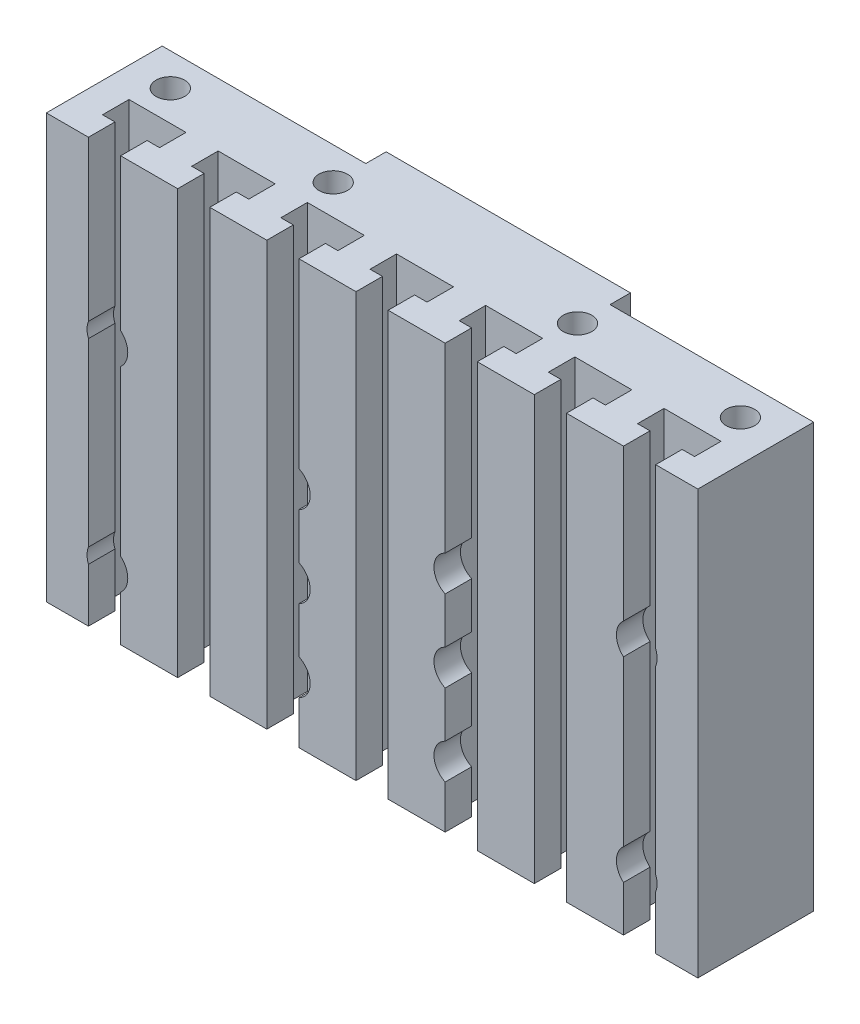
SolidWorks part; units mm, degrees
ref_plane "Front Plane" through (0, 0, 0) normal (0, 0, 1) x (1, 0, 0)
ref_plane "Top Plane" through (0, 0, 0) normal (0, 1, 0) x (1, 0, 0)
ref_plane "Right Plane" through (0, 0, 0) normal (1, 0, 0) x (0, 0, -1)
sketch "Sketch1" plane through (0, 0, 0) normal (0, 0, 1) x (1, 0, 0)
  line L0 (0, 52) -> (0, -52) construction
  line L1 (-80, 52) -> (80, 52)
  line L2 (-80, 52) -> (-80, -52)
  line L3 (-80, -52) -> (80, -52)
  line L4 (80, 52) -> (80, -52)
  line L5 (-80, 52) -> (80, -52) construction
  line L6 (-80, -52) -> (80, 52) construction
  line L7 (20, 52) -> (20, -55.7258) construction
  circle A0 centre (20, -37) radius 2.5
  circle A1 centre (-20, -37) radius 2.5
  circle A2 centre (20, -17) radius 2.5
  circle A3 centre (20, 3) radius 2.5
  circle A4 centre (-20, 3) radius 2.5
  circle A5 centre (-20, -17) radius 2.5
  point P0 (0, 0)
  dimension "D4" = 5
  dimension "D1" = 160
  dimension "D2" = 104
  dimension "D3" = 40
  dimension "D5" = 15
  dimension "D6" = 20
  dimension "D7" = 20
extrude "Boss-Extrude1" add sketch "Sketch1" along normal blind 28.45
sketch "Sketch2" plane through (0, 52, 0) normal (0, 1, 0) x (1, 0, 0)
  line L0 (80, -28.45) -> (-80, -28.45) construction
  line L1 (-3.95, -28.45) -> (3.95, -28.45)
  line L2 (-3.95, -28.45) -> (-3.95, -21.95)
  line L4 (3.95, -28.45) -> (3.95, -21.95)
  line L5 (3.95, -21.95) -> (7, -21.95)
  line L6 (-7, -15.45) -> (7, -15.45)
  line L7 (-7, -15.45) -> (-7, -21.95)
  line L8 (-7, -21.95) -> (-3.95, -21.95)
  line L9 (7, -15.45) -> (7, -21.95)
  line L10 (0, 0) -> (0, -28.45) construction
  line L11 (80, 0) -> (-80, 0) construction
  line L12 (25.85, -28.45) -> (25.85, -21.95)
  line L13 (17.95, -28.45) -> (25.85, -28.45)
  line L14 (25.85, -21.95) -> (28.9, -21.95)
  line L15 (28.9, -15.45) -> (28.9, -21.95)
  line L16 (14.9, -15.45) -> (28.9, -15.45)
  line L17 (14.9, -15.45) -> (14.9, -21.95)
  line L18 (14.9, -21.95) -> (17.95, -21.95)
  line L19 (17.95, -28.45) -> (17.95, -21.95)
  line L20 (47.75, -28.45) -> (47.75, -21.95)
  line L21 (39.85, -28.45) -> (47.75, -28.45)
  line L22 (47.75, -21.95) -> (50.8, -21.95)
  line L23 (50.8, -15.45) -> (50.8, -21.95)
  line L24 (36.8, -15.45) -> (50.8, -15.45)
  line L25 (36.8, -15.45) -> (36.8, -21.95)
  line L26 (36.8, -21.95) -> (39.85, -21.95)
  line L27 (39.85, -28.45) -> (39.85, -21.95)
  line L28 (69.65, -28.45) -> (69.65, -21.95)
  line L29 (61.75, -28.45) -> (69.65, -28.45)
  line L30 (69.65, -21.95) -> (72.7, -21.95)
  line L31 (72.7, -15.45) -> (72.7, -21.95)
  line L32 (58.7, -15.45) -> (72.7, -15.45)
  line L33 (58.7, -15.45) -> (58.7, -21.95)
  line L34 (58.7, -21.95) -> (61.75, -21.95)
  line L35 (61.75, -28.45) -> (61.75, -21.95)
  line L36 (-28.9, -15.45) -> (-28.9, -21.95)
  line L37 (-28.9, -21.95) -> (-25.85, -21.95)
  line L38 (-25.85, -28.45) -> (-25.85, -21.95)
  line L39 (-28.9, -15.45) -> (-14.9, -15.45)
  line L40 (-14.9, -15.45) -> (-14.9, -21.95)
  line L41 (-17.95, -28.45) -> (-17.95, -21.95)
  line L42 (-25.85, -28.45) -> (-17.95, -28.45)
  line L43 (-17.95, -21.95) -> (-14.9, -21.95)
  line L44 (-50.8, -15.45) -> (-50.8, -21.95)
  line L45 (-50.8, -21.95) -> (-47.75, -21.95)
  line L46 (-47.75, -28.45) -> (-47.75, -21.95)
  line L47 (-50.8, -15.45) -> (-36.8, -15.45)
  line L48 (-36.8, -15.45) -> (-36.8, -21.95)
  line L49 (-39.85, -28.45) -> (-39.85, -21.95)
  line L50 (-47.75, -28.45) -> (-39.85, -28.45)
  line L51 (-39.85, -21.95) -> (-36.8, -21.95)
  line L52 (-72.7, -15.45) -> (-72.7, -21.95)
  line L53 (-72.7, -21.95) -> (-69.65, -21.95)
  line L54 (-69.65, -28.45) -> (-69.65, -21.95)
  line L55 (-72.7, -15.45) -> (-58.7, -15.45)
  line L56 (-58.7, -15.45) -> (-58.7, -21.95)
  line L57 (-61.75, -28.45) -> (-61.75, -21.95)
  line L58 (-69.65, -28.45) -> (-61.75, -28.45)
  line L59 (-61.75, -21.95) -> (-58.7, -21.95)
  point P14 (0, -15.45)
  dimension "D1" = 14
  dimension "D2" = 7.9
  dimension "D3" = 6.5
  dimension "D4" = 6.5
  dimension "D6" = 7.9
  dimension "D8" = 7.9
  dimension "D5" = 4
  dimension "D7" = 4
extrude "Cut-Extrude1" cut sketch "Sketch2" against normal through all
sketch "Sketch5" plane through (0, 0, 0) normal (0, 0, -1) x (-1, 0, 0)
  line L0 (0, 52) -> (0, -52) construction
  line L1 (-80, 52) -> (80, 52) construction
  line L2 (80, -52) -> (-80, -52) construction
  line L4 (-30, -52) -> (30, -52)
  line L5 (-30, -52) -> (-30, 52)
  line L6 (-30, 52) -> (30, 52)
  line L7 (30, -52) -> (30, 52)
  point P10 (0, 52)
  dimension "D1" = 60
extrude "Boss-Extrude2" add sketch "Sketch5" along normal blind 5
sketch "Sketch3" plane through (0, 0, 28.45) normal (0, 0, 1) x (1, 0, 0)
  circle A0 centre (-20, 3) radius 4.8
  circle A1 centre (20, 3) radius 4.8
  circle A2 centre (-20, -17) radius 4.8
  circle A3 centre (20, -17) radius 4.8
  circle A4 centre (-20, -37) radius 4.8
  circle A5 centre (20, -37) radius 4.8
  dimension "D1" = 9.6
extrude "Cut-Extrude2" cut sketch "Sketch3" against normal blind 7
sketch "Sketch4" plane through (0, 0, 15.45) normal (0, 0, 1) x (1, 0, 0)
  circle A0 centre (-20, 3) radius 4.8
  circle A1 centre (20, 3) radius 4.8
  circle A2 centre (-20, -17) radius 4.8
  circle A3 centre (20, -17) radius 4.8
  circle A4 centre (-20, -37) radius 4.8
  circle A5 centre (20, -37) radius 4.8
  dimension "D1" = 9.6
extrude "Cut-Extrude3" cut sketch "Sketch4" against normal blind 13.35 from surface starting at face at (-16.515, -10.2, 21.95)
sketch "Sketch6" plane through (0, 0, 0) normal (0, 0, 1) x (1, 0, 0)
  circle A0 centre (-20, 3) radius 2.5
  circle A1 centre (20, 3) radius 2.5
  circle A2 centre (-20, -17) radius 2.5
  circle A3 centre (20, -17) radius 2.5
  circle A4 centre (20, -37) radius 2.5
  circle A5 centre (-20, -37) radius 2.5
  dimension "D1" = 5
extrude "Cut-Extrude4" cut sketch "Sketch6" against normal through all
sketch "Sketch7" plane through (0, 52, 0) normal (0, 1, 0) x (1, 0, 0)
  line L0 (-80, -8) -> (80, -8) construction
  line L1 (-80, -28.45) -> (-80, 0) construction
  line L2 (80, -28.45) -> (80, 0) construction
  line L4 (-30, 0) -> (-80, 0) construction
  line L6 (0, 5) -> (0, -15.45) construction
  line L7 (-30, 5) -> (30, 5) construction
  line L8 (7, -15.45) -> (-7, -15.45) construction
  circle A0 centre (-70, -8) radius 3.5
  circle A1 centre (-30, -8) radius 3.5
  circle A2 centre (70, -8) radius 3.5
  circle A3 centre (30, -8) radius 3.5
  dimension "D1" = 7
  dimension "D3" = 40
  dimension "D2" = 10
  dimension "D4" = 8
extrude "Cut-Extrude5" cut sketch "Sketch7" against normal blind 12
sketch "Sketch8" plane through (0, -52, 0) normal (0, -1, 0) x (1, 0, 0)
  line L0 (80, 8) -> (-80, 8) construction
  line L1 (80, 28.45) -> (80, 0) construction
  line L2 (-80, 28.45) -> (-80, 0) construction
  line L3 (30, 0) -> (80, 0) construction
  line L6 (0, -5) -> (0, 15.45) construction
  line L7 (30, -5) -> (-30, -5) construction
  line L8 (7, 15.45) -> (-7, 15.45) construction
  circle A0 centre (70, 8) radius 3.5
  circle A1 centre (30, 8) radius 3.5
  circle A2 centre (-30, 8) radius 3.5
  circle A3 centre (-70, 8) radius 3.5
  dimension "D1" = 7
  dimension "D2" = 10
  dimension "D3" = 40
  dimension "D4" = 8
extrude "Cut-Extrude6" cut sketch "Sketch8" against normal blind 12
sketch "Sketch9" plane through (0, 0, 28.45) normal (0, 0, 1) x (1, 0, 0)
  line L0 (0, 47.1529) -> (0, -45.7832) construction
  line L1 (-80, -52) -> (-69.65, -52) construction
  line L2 (-65, 11) -> (65, 11) construction
  line L3 (-65, 11) -> (-65, -37) construction
  line L4 (-65, -37) -> (65, -37) construction
  line L5 (65, 11) -> (65, -37) construction
  circle A0 centre (-65, 11) radius 5
  circle A1 centre (-65, -37) radius 5
  circle A2 centre (65, -37) radius 5
  circle A3 centre (65, 11) radius 5
  point P3 (0, 11)
  point P8 (-65, -13)
  dimension "D3" = 10
  dimension "D1" = 130
  dimension "D2" = 48
  dimension "D4" = 15
extrude "Cut-Extrude7" cut sketch "Sketch9" against normal blind 26
